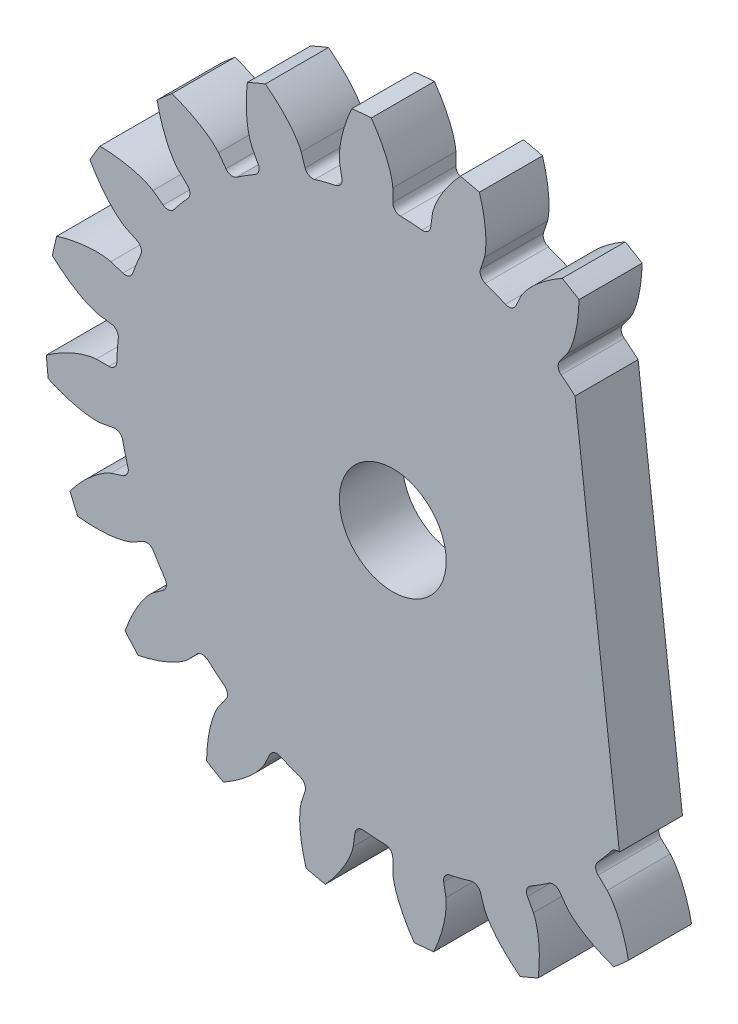
SolidWorks part; units mm, degrees
material "Acrylic (Medium-high impact)"
ref_plane "Front Plane" through (0, 0, 0) normal (0, 0, 1) x (1, 0, 0)
ref_plane "Top Plane" through (0, 0, 0) normal (0, 1, 0) x (1, 0, 0)
ref_plane "Right Plane" through (0, 0, 0) normal (1, 0, 0) x (0, 0, -1)
sketch "Sketch1" plane through (0, 0, 0) normal (0, 0, 1) x (1, 0, 0)
  line L0 (14.0954, 0) -> (13.125, 0)
  line L1 (16.4331, 1.4848) -> (-16.4331, -1.4848)
  line L2 (0, 0) -> (14.9983, 0.2236) construction
  circle A0 centre (0, 0) radius 14.0954 construction
  circle A1 centre (0, 0) radius 16.5
  circle A2 centre (0, 0) radius 13.125
  circle A3 centre (0, 0) radius 15 construction
  spline S0 degree 4 poles (14.0954, 0) (14.1058, 0.0002) (14.135, 0.0015) (14.1901, 0.0067) (14.2796, 0.0189) (14.393, 0.04) (14.5385, 0.0738) (14.7082, 0.1216) (14.8927, 0.1826) (15.0909, 0.258) (15.2861, 0.341) (15.4783, 0.4311) (15.6673, 0.5274) (15.8931, 0.6515) (16.1593, 0.8107) (16.4633, 1.0115) (16.799, 1.2565) (17.1307, 1.524) (17.4482, 1.8017) (17.758, 2.0982) (18.0498, 2.3963) (18.3408, 2.7214) (18.6032, 3.0295) (18.8829, 3.3909) (19.1045, 3.6874) (19.381, 4.0951) (19.5394, 4.3407) (19.7191, 4.6335) (19.7959, 4.7664) (19.8433, 4.8482) knots 0 0 0 0 0 0.005377 0.015084 0.028532 0.04661 0.064855 0.092111 0.119476 0.146842 0.174209 0.201575 0.228941 0.256307 0.307035 0.361767 0.4165 0.471232 0.525964 0.580697 0.635429 0.690161 0.744894 0.799626 0.854358 0.909091 0.954545 1 1 1 1 1 construction
  spline S1 degree 4 poles (14.0954, 0) (14.1058, 0.0002) (14.135, 0.0015) (14.1901, 0.0067) (14.2796, 0.0189) (14.393, 0.04) (14.5385, 0.0738) (14.7082, 0.1216) (14.8927, 0.1826) (15.0909, 0.258) (15.2861, 0.341) (15.4783, 0.4311) (15.6673, 0.5274) (15.8931, 0.6515) (16.1593, 0.8107) (16.4633, 1.0115) (16.799, 1.2565) (17.1307, 1.524) (17.4482, 1.8017) (17.758, 2.0982) (18.0498, 2.3963) (18.3408, 2.7214) (18.6032, 3.0295) (18.8829, 3.3909) (19.1045, 3.6874) (19.321, 4.0067) (19.4245, 4.1639) (19.4766, 4.2451) knots 0 0 0 0 0 0.005377 0.015084 0.028532 0.04661 0.064855 0.092111 0.119476 0.146842 0.174209 0.201575 0.228941 0.256307 0.307035 0.361767 0.4165 0.471232 0.525964 0.580697 0.635429 0.690161 0.744894 0.799626 0.854358 0.909091 0.909091 0.909091 0.909091 0.909091
  dimension "D1" = 28.1908
  dimension "D2" = 33
  dimension "D3" = 26.25
  dimension "D5" = 30
  dimension "D4" = 4.309
extrude "Boss-Extrude3" add sketch "Sketch1" along normal blind 3 contours L1 A2 | A2 L1 | L0 S1 A1 L1 A2
mirror "Mirror2" about plane through (0, 0, 3) normal (0.09, -0.9959, 0) of "Boss-Extrude3"
fillet "Fillet1" radius 0.375 2 edges at (12.9124, 2.3526, 1.5) (13.125, 0, 1.5)
pattern_circular "CirPattern8" count 20 over 360 about axis through (0, 0, 3) along (0, 0, -1) of "Boss-Extrude3", "Mirror2", "Fillet1"
sketch "Sketch3" plane through (0, 0, 3) normal (0, 0, 1) x (1, 0, 0)
  circle A0 centre (0, 0) radius 2.54
  dimension "D1" = 5.08
extrude "Cut-Extrude2" cut sketch "Sketch3" against normal through all
ref_plane "Plane1" through (16.3846, 1.9484, 3) normal (0.993, 0.1181, 0) x (0, 0, -1)
sketch "Sketch4" plane through (16.3846, 1.9484, 3) normal (0.993, 0.1181, 0) x (0, 0, -1)
  line L1 (-4.5487, 25.4) -> (4.5487, 25.4)
  line L2 (-4.5487, 25.4) -> (-4.5487, -25.4)
  line L3 (-4.5487, -25.4) -> (4.5487, -25.4)
  line L4 (4.5487, 25.4) -> (4.5487, -25.4)
  line L5 (-4.5487, 25.4) -> (4.5487, -25.4) construction
  line L6 (-4.5487, -25.4) -> (4.5487, 25.4) construction
  point P0 (0, 0)
  dimension "D1" = 50.8
extrude "Cut-Extrude3" cut sketch "Sketch4" against normal blind 5.842
sketch "Sketch5" plane through (10.5834, 1.2585, 0) normal (0.993, 0.1181, 0) x (0, 0, -1)
  line L1 (-3, 8.7996) -> (0, 8.7996)
  line L2 (-3, 8.7996) -> (-3, -9.7841)
  line L3 (-3, -9.7841) -> (0, -9.7841)
  line L4 (0, 8.7996) -> (0, -9.7841)
extrude "Cut-Extrude4" cut sketch "Sketch5" against normal blind 0.889
equation "\"d\"= 30mm'Pitch diameter"
equation "\"N\"= 20'Number of teeth"
equation "\"bl\"= 0.1mm'Backlash"
equation "\"pa\"= 20deg'Pressure angle (deg)"
equation "\"pc\"= ( 3.1415 * \"d\" ) / \"N\"\t'Circular pitch"
equation "\"m\"= \"d\" / \"N\"\t\t\t'module"
equation "\"P\"= \"N\" / \"d\"\t\t\t'Diametral pitch"
equation "\"a\"= 1/\"P\"\t\t\t'Addendum distance"
equation "\"b\"= 1.25 / \"P\"'Dedendum distance"
equation "\"rb\"= (\"d\"/2)*cos(\"pa\")\t\t'base circle radius"
equation "\"cp\"= 3.1415/\"P\"\t\t'Circular pitch"
equation "\"t\"= ( \"cp\" / 2 ) - \"bl\"'tooth tickness"
equation "\"c\"=\"b\"-\"a\"\t\t\t'Clearance"
equation "\"facewidth\"= 3mm'face width"
equation "\"rbd\"= \"rb\" * 2'base circle diameter"
equation "\"D1@Sketch1\"=\"rbd\""
equation "\"D2@Sketch1\"= \"d\" + (\"a\" * 2)"
equation "\"D3@Sketch1\" = \"ded\""
equation "\"D4@Sketch1\"= ((\"t\" /2) / (\"d\"/2)) * (180/3.1415)"
equation "\"D1@Boss-Extrude3\"=\"facewidth\""
equation "\"D1@Fillet1\"=\"c\""
equation "\"D1@CirPattern8\"=\"N\""
equation "\"D5@Sketch1\"=\"d\""
equation "\"ded1\"= \"d\" - 2 * ( ( ( \"d\" / 2 ) - \"rb\" ) + ( 0.5 * ( 1.25 / \"P\" ) ) )"
equation "\"ded2\"= \"d\" - ( \"b\" * 2 )"
equation "\"ded\"= IIF ( \"rb\" < ( \"ded2\" / 2 ) , \"ded1\" , \"ded2\" )"
equation "\"shaftdia\"= 0.2in"
equation "\"D1@Sketch3\"=\"shaftdia\""
